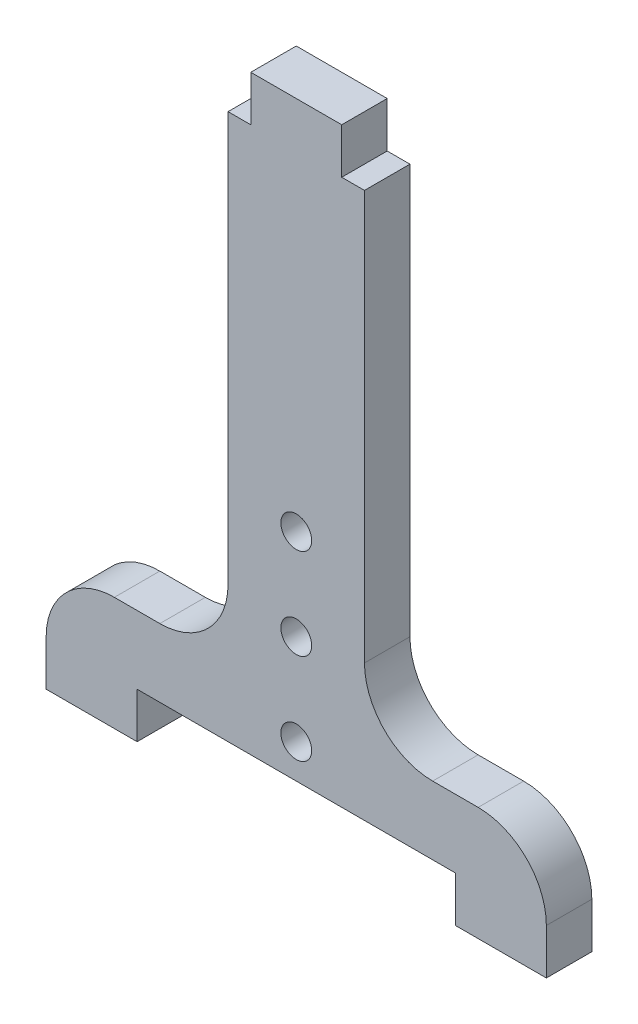
SolidWorks part; units mm, degrees
material "Custom Plastic"
ref_plane "Front Plane" through (0, 0, 0) normal (0, 0, 1) x (1, 0, 0)
ref_plane "Top Plane" through (0, 0, 0) normal (0, 1, 0) x (1, 0, 0)
ref_plane "Right Plane" through (0, 0, 0) normal (1, 0, 0) x (0, 0, -1)
sketch "Sketch1" plane through (0, 0, 0) normal (0, 0, 1) x (1, 0, 0)
  line L1 (-34.925, -38.1) -> (34.925, -38.1)
  line L2 (-34.925, -38.1) -> (-34.925, 38.1)
  line L3 (-34.925, 38.1) -> (34.925, 38.1)
  line L4 (34.925, -38.1) -> (34.925, 38.1)
  line L5 (-34.925, -38.1) -> (34.925, 38.1) construction
  line L6 (-34.925, 38.1) -> (34.925, -38.1) construction
  point P0 (0, 0)
  dimension "D1" = 69.85
  dimension "D2" = 76.2
extrude "Base" add sketch "Sketch1" along normal blind 6.35
sketch "Sketch6" plane through (0, 0, 6.35) normal (0, 0, 1) x (1, 0, 0)
  line L0 (34.925, 38.1) -> (-34.925, 38.1) construction
  line L1 (-6.35, 38.1) -> (6.35, 38.1)
  line L2 (-6.35, 38.1) -> (-6.35, 44.45)
  line L3 (-6.35, 44.45) -> (6.35, 44.45)
  line L4 (6.35, 38.1) -> (6.35, 44.45)
  line L5 (0, -38.1) -> (0, 38.1) construction
  line L6 (-34.925, -38.1) -> (34.925, -38.1) construction
  line L7 (22.225, -38.1) -> (22.225, -44.45)
  line L8 (-34.925, -38.1) -> (-22.225, -38.1)
  line L9 (-34.925, -38.1) -> (-34.925, -44.45)
  line L10 (-34.925, -44.45) -> (-22.225, -44.45)
  line L11 (-22.225, -38.1) -> (-22.225, -44.45)
  line L12 (34.925, -44.45) -> (22.225, -44.45)
  line L13 (34.925, -38.1) -> (34.925, -44.45)
  line L14 (34.925, -38.1) -> (22.225, -38.1)
  point P7 (0, 38.1)
  dimension "D1" = 12.7
  dimension "D2" = 6.35
  dimension "D3" = 6.35
  dimension "D4" = 12.7
extrude "Boss-Extrude1" add sketch "Sketch6" against normal blind 6.35
sketch "Sketch7" plane through (0, 0, 6.35) normal (0, 0, 1) x (1, 0, 0)
  line L1 (-6.35, 38.1) -> (-34.925, 38.1) construction
  line L2 (-9.525, 38.1) -> (-9.525, -28.575)
  line L4 (-9.525, -28.575) -> (-34.925, -28.575)
  line L5 (-34.925, 38.1) -> (-34.925, -44.45) construction
  line L6 (-22.225, -38.1) -> (22.225, -38.1) construction
  line L7 (0, -38.1) -> (0, 44.45) construction
  line L8 (6.35, 44.45) -> (-6.35, 44.45) construction
  line L9 (-9.525, 38.1) -> (-34.925, 38.1)
  line L10 (-34.925, 38.1) -> (-34.925, -28.575)
  line L11 (34.925, 38.1) -> (34.925, -28.575)
  line L12 (9.525, 38.1) -> (34.925, 38.1)
  line L13 (9.525, -28.575) -> (34.925, -28.575)
  line L15 (9.525, 38.1) -> (9.525, -28.575)
  dimension "D1" = 9.525
  dimension "D2" = 9.525
extrude "Cut-Extrude1" cut sketch "Sketch7" against normal through all
fillet "Fillet1" radius 9.525 4 edges at (9.525, -28.575, 3.175) (-9.525, -28.575, 3.175) (34.925, -28.575, 3.175) (-34.925, -28.575, 3.175)
sketch "Motor mounting sketch" plane through (0, 0, 6.35) normal (0, 0, 1) x (1, 0, 0)
  line L0 (-34.925, -33.3375) -> (34.925, -33.3375) construction
  line L1 (34.925, -44.45) -> (34.925, -38.1) construction
  line L2 (-34.925, -38.1) -> (-34.925, -44.45) construction
  line L3 (0, 38.1) -> (0, -38.1) construction
  line L5 (-22.225, -38.1) -> (22.225, -38.1) construction
  line L7 (-22.225, -38.1) -> (22.225, -38.1) construction
  line L9 (9.525, 38.1) -> (6.35, 38.1) construction
  point P12 (0, -33.3375)
  point P15 (0, 4.7625)
  point P20 (0, -20.6375)
  point P21 (0, -7.9375)
  dimension "D1" = 4.7625
  dimension "D2" = 12.7
  dimension "D4" = 12.7
  dimension "D5" = 12.7
hole_wizard "#8 Clearance Hole1" positions "Sketch5" profile "Sketch4" hole size "#8" standard "ANSI Inch" end condition through all
sketch "Sketch5" plane through (0, 0, 0) normal (0, 0, -1) x (-1, 0, 0)
  point P3 (0, -33.3375)
  point P31 (0, -20.6375)
  point P34 (0, -7.9375)
sketch "Sketch4" plane through (0, -33.3375, 0) normal (1, 0, 0) x (0, 1, 0)
  line L0 (0, 0) -> (0, 6.35)
  line L1 (0, 6.35) -> (2.1526, 6.35)
  line L2 (2.1526, 6.35) -> (2.1526, 0)
  line L5 (2.1526, 0) -> (0, 0)
  line L11 (0, -6.35) -> (0, 107.95) construction
  dimension "Thru Hole Dia." = 4.3053
  dimension "Thru Hole Depth" = 6.35
equation "\"MAT_THICKNESS\"=0.25"
equation "\"D1@Base\"=\"MAT_THICKNESS\""
equation "\"D2@Sketch6\" = \"MAT_THICKNESS\""
equation "\"D3@Sketch6\"=\"MAT_THICKNESS\""
equation "\"D1@Boss-Extrude1\"=\"MAT_THICKNESS\""
